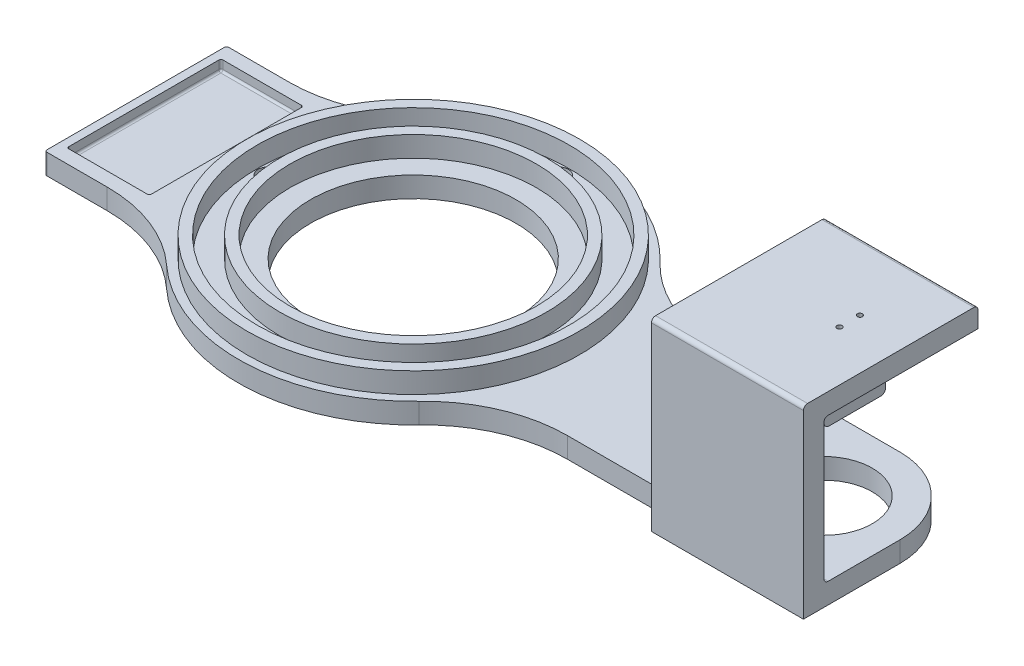
SolidWorks part; units mm, degrees
material "Plástico personalizado"
ref_plane "Alzado" through (0, 0, 0) normal (0, 0, 1) x (1, 0, 0)
ref_plane "Planta" through (0, 0, 0) normal (0, 1, 0) x (1, 0, 0)
ref_plane "Vista lateral" through (0, 0, 0) normal (1, 0, 0) x (0, 0, -1)
sketch "Croquis1" plane through (0, 0, 0) normal (0, 1, 0) x (1, 0, 0)
  line L0 (0, 0) -> (181.3793, 0) construction
  line L1 (0, 0) -> (200, 0) construction
  line L2 (0, 37) -> (200, 37)
  line L3 (0, -37) -> (200, -37)
  line L5 (-72.5705, 44.2552) -> (-135.1432, 44.2552)
  line L6 (-72.5705, 44.2552) -> (-72.5705, -44.2552)
  line L7 (-72.5705, -44.2552) -> (-135.1432, -44.2552)
  line L8 (-135.1432, 44.2552) -> (-135.1432, -44.2552)
  line L9 (-72.5705, 44.2552) -> (-135.1432, -44.2552) construction
  line L10 (-72.5705, -44.2552) -> (-135.1432, 44.2552) construction
  line L11 (200, 0) -> (237, 0)
  line L12 (200, 0) -> (200, -37)
  line L13 (200, -37) -> (237, -37)
  line L14 (237, 0) -> (237, -37)
  circle A0 centre (0, 0) radius 50
  circle A1 centre (0, 0) radius 85
  arc A2 (0, 37) -> (0, -37) centre (0, 0) ccw
  arc A3 (200, -37) -> (200, 37) centre (200, 0) ccw
  circle A4 centre (200, 0) radius 23.5
  point P6 (100, 0)
  point P13 (-103.8568, 0)
  dimension "D1" = 100
  dimension "D2" = 170
  dimension "D4" = 47
  dimension "D5" = 37
  dimension "D3" = 200
extrude "Saliente-Extruir1" add sketch "Croquis1" along normal blind 10 contours L2 A1 L3 A0 | L3 A1 L2 A0 | L3 A3 L2 A1 A4 | A4 L12 A3 L11 | A3 L13 L14 | L6 L5 L8 L7 region at (-52.2612, 0, 0) region at (63.3815, 0, 0) region at (142.0204, 0, -1.4794) region at (219.5774, 0, 19.5774) region at (228.7354, 0, 28.7354)
fillet "Redondeo1" radius 70 4 edges at (76.5245, 5, -37) (76.5245, 5, 37) (-72.5705, 5, -44.2552) (-72.5705, 5, 44.2552)
sketch "Croquis2" plane through (0, 10, 0) normal (0, 1, 0) x (1, 0, 0)
  circle A0 centre (0, 0) radius 81
  circle A1 centre (0, 0) radius 76
  dimension "D1" = 152
  dimension "D2" = 162
extrude "Saliente-Extruir2" add sketch "Croquis2" along normal blind 10
sketch "Croquis8" plane through (0, 0, 37) normal (0, 0, 1) x (1, 0, 0)
  line L6 (112.1428, 10) -> (237, 10) construction
  line L7 (237, 0) -> (163, 0)
  line L8 (237, 0) -> (237, 10)
  line L9 (237, 10) -> (163, 10)
  line L10 (163, 0) -> (163, 10)
  dimension "D1" = 74
extrude "Saliente-Extruir4" add sketch "Croquis8" along normal blind 10
sketch "Croquis9" plane through (0, 10, 0) normal (0, 1, 0) x (1, 0, 0)
  line L7 (237, 0) -> (237, -47) construction
  line L8 (163, -47) -> (237, -47)
  line L9 (163, -47) -> (163, -37)
  line L10 (163, -37) -> (237, -37)
  line L11 (237, -47) -> (237, -37)
extrude "Saliente-Extruir5" add sketch "Croquis9" along normal blind 80
sketch "Croquis10" plane through (0, 0, 37) normal (0, 0, -1) x (-1, 0, 0)
  line L0 (-163, 90) -> (-163, 10) construction
  line L1 (-237, 90) -> (-163, 90)
  line L2 (-237, 90) -> (-237, 80)
  line L3 (-237, 80) -> (-163, 80)
  line L4 (-163, 90) -> (-163, 80)
  dimension "D1" = 10
extrude "Saliente-Extruir6" add sketch "Croquis10" along normal blind 75
fillet "Redondeo3" radius 2 1 edges at (200, 10, 37)
fillet "Redondeo4" radius 2 1 edges at (200, 80, 37)
fillet "Redondeo5" radius 2 1 edges at (200, 90, 47)
fillet "Redondeo6" radius 2 1 edges at (200, 90, -38)
sketch "Croquis12" plane through (0, 10, 0) normal (0, 1, 0) x (1, 0, 0)
  circle A0 centre (0, 0) radius 60
  circle A1 centre (0, 0) radius 65
  dimension "D1" = 120
  dimension "D2" = 130
extrude "Saliente-Extruir12" add sketch "Croquis12" along normal blind 10
sketch "Croquis6" plane through (0, 10, 0) normal (0, 1, 0) x (1, 0, 0)
  circle A0 centre (200, 0) radius 23.5
  circle A1 centre (200, 0) radius 8.5
  dimension "D1" = 17
  dimension "D2" = 47
sketch "Croquis13" plane through (0, 10, 0) normal (0, 1, 0) x (1, 0, 0)
  line L1 (-7.5, 81) -> (7.5, 81)
  line L2 (-7.5, 81) -> (-7.5, -81)
  line L3 (-7.5, -81) -> (7.5, -81)
  line L4 (7.5, 81) -> (7.5, -81)
  line L5 (-7.5, 81) -> (7.5, -81) construction
  line L6 (-7.5, -81) -> (7.5, 81) construction
  line L7 (-81, 7.5) -> (81, 7.5)
  line L8 (-81, 7.5) -> (-81, -7.5)
  line L9 (-81, -7.5) -> (81, -7.5)
  line L10 (81, 7.5) -> (81, -7.5)
  line L11 (-81, 7.5) -> (81, -7.5) construction
  line L12 (-81, -7.5) -> (81, 7.5) construction
  circle A1 centre (0, 70.5) radius 5
  circle A3 centre (0, -70.5) radius 5
  circle A4 centre (-70.5, 0) radius 5
  circle A5 centre (70.5, 0) radius 5
  point P0 (0, 0)
  point P6 (0, 0)
  dimension "D1" = 162
  dimension "D5" = 10
  dimension "D6" = 10.5
  dimension "D7" = 10
  dimension "D9" = 10
  dimension "D11" = 10
  dimension "D12" = 10.5
  dimension "D2" = 162
  dimension "D3" = 15
  dimension "D4" = 15
  dimension "D8" = 10.5
  dimension "D10" = 10.5
extrude "Cortar-Extruir1" cut sketch "Croquis13" against normal up to surface (10 mm away) contours A4 | A1 | A5 | A3 region at (0, 10, -70.5) region at (0, 10, 70.5) region at (-70.5, 10, 0) region at (70.5, 10, 0) up to face at (50.7287, 0, 5.7558)
sketch "Croquis14" plane through (0, 80, 0) normal (0, -1, 0) x (1, 0, 0)
  line L1 (168.05, 10) -> (210.05, 10)
  line L2 (168.05, 10) -> (168.05, -10)
  line L3 (168.05, -10) -> (210.05, -10)
  line L4 (210.05, 10) -> (210.05, -10)
  line L5 (168.05, 10) -> (210.05, -10) construction
  line L6 (168.05, -10) -> (210.05, 10) construction
  line L7 (163.05, 15) -> (215.05, 15)
  line L8 (163.05, 15) -> (163.05, -15)
  line L9 (163.05, -15) -> (215.05, -15)
  line L10 (215.05, 15) -> (215.05, -15)
  line L11 (163.05, 15) -> (215.05, -15) construction
  line L12 (163.05, -15) -> (215.05, 15) construction
  line L13 (163.05, 10) -> (168.05, 10)
  line L14 (163.05, 10) -> (163.05, -10)
  line L15 (163.05, -10) -> (168.05, -10)
  line L16 (168.05, 10) -> (168.05, -10)
  line L17 (163.05, 10) -> (168.05, -10) construction
  line L18 (163.05, -10) -> (168.05, 10) construction
  circle A0 centre (212.55, 4.95) radius 1.25
  circle A1 centre (212.55, -4.95) radius 1.25
  point P0 (189.05, 0)
  point P6 (165.55, 0)
  point P8 (189.05, 0)
  dimension "D8" = 2.5
  dimension "D9" = 2.5
  dimension "D10" = 5.05
  dimension "D1" = 10.05
  dimension "D2" = 20
  dimension "D3" = 42
  dimension "D4" = 5
  dimension "D5" = 5
  dimension "D6" = 20
  dimension "D7" = 9.9
  dimension "D11" = 5.05
  dimension "D12" = 2.5
extrude "Saliente-Extruir13" add sketch "Croquis14" along normal blind 26.7 contours L15 L8 L9 L10 L7 L13 L1 L4 L3 A1 A0 region at (165.55, 80, 10.6003)
fillet "Redondeo7" radius 10 3 edges at (189.05, 80, -15) (215.05, 80, 0) (189.05, 80, 15)
sketch "Croquis15" plane through (0, 53.3, 0) normal (0, -1, 0) x (1, 0, 0)
  circle A0 centre (212.55, 4.95) radius 1.25
  circle A1 centre (212.55, -4.95) radius 1.25
extrude "Cortar-Extruir2" cut sketch "Croquis15" against normal up to surface (36.7 mm away) up to face at (200, 90, 4.5)
fillet "Redondeo9" radius 2.5 2 edges at (189.05, 53.3, 15) (189.05, 53.3, -15)
sketch "Croquis17" plane through (237, 0, 0) normal (1, 0, 0) x (0, 0, -1)
  line L0 (15, 70) -> (-15, 70) construction
  line L1 (-3.5, 77) -> (3.5, 77)
  line L2 (-3.5, 77) -> (-3.5, 72)
  line L3 (-3.5, 72) -> (3.5, 72)
  line L4 (3.5, 77) -> (3.5, 72)
  line L5 (-25, 80) -> (25, 80) construction
  point P7 (0, 70)
  point P10 (0, 77)
  dimension "D1" = 7
  dimension "D2" = 5
  dimension "D3" = 3
extrude "Cortar-Extruir3" cut sketch "Croquis17" against normal up to surface (26.95 mm away) up to face at (210.05, 66.65, 0)
sketch "Croquis18" plane through (0, 10, 0) normal (0, 1, 0) x (1, 0, 0)
  line L1 (-135.1432, 44.2552) -> (-81, 44.2552)
  line L2 (-135.1432, 44.2552) -> (-135.1432, -44.2552)
  line L3 (-135.1432, -44.2552) -> (-81, -44.2552)
  line L4 (-81, 44.2552) -> (-81, -44.2552)
  line L5 (-131.1432, 37.5052) -> (-91, 37.5052)
  line L6 (-131.1432, 37.5052) -> (-131.1432, -37.4948)
  line L7 (-131.1432, -37.4948) -> (-91, -37.4948)
  line L8 (-91, 37.5052) -> (-91, -37.4948)
  circle A0 centre (0, 0) radius 81 construction
  point P7 (-81, 0)
  dimension "D1" = 6.75
  dimension "D2" = 6.7604
  dimension "D3" = 75
  dimension "D4" = 10
  dimension "D5" = 4
extrude "Cortar-Extruir4" cut sketch "Croquis18" against normal blind 5 contours L8 L5 L6 L7 region at (-111.0716, 10, -0.0052)
fillet "Redondeo10" radius 1 8 edges at (-91, 7.5, 37.4948) (-131.1432, 7.5, 37.4948) (-131.1432, 7.5, -37.5052) (-91, 7.5, -37.5052) (-111.0716, 5, 37.4948) (-131.1432, 5, -0.0052) (-91, 5, -0.0052) (-111.0716, 5, -37.5052)
fillet "Redondeo11" radius 1 2 edges at (-135.1432, 5, 44.2552) (-135.1432, 5, -44.2552)
